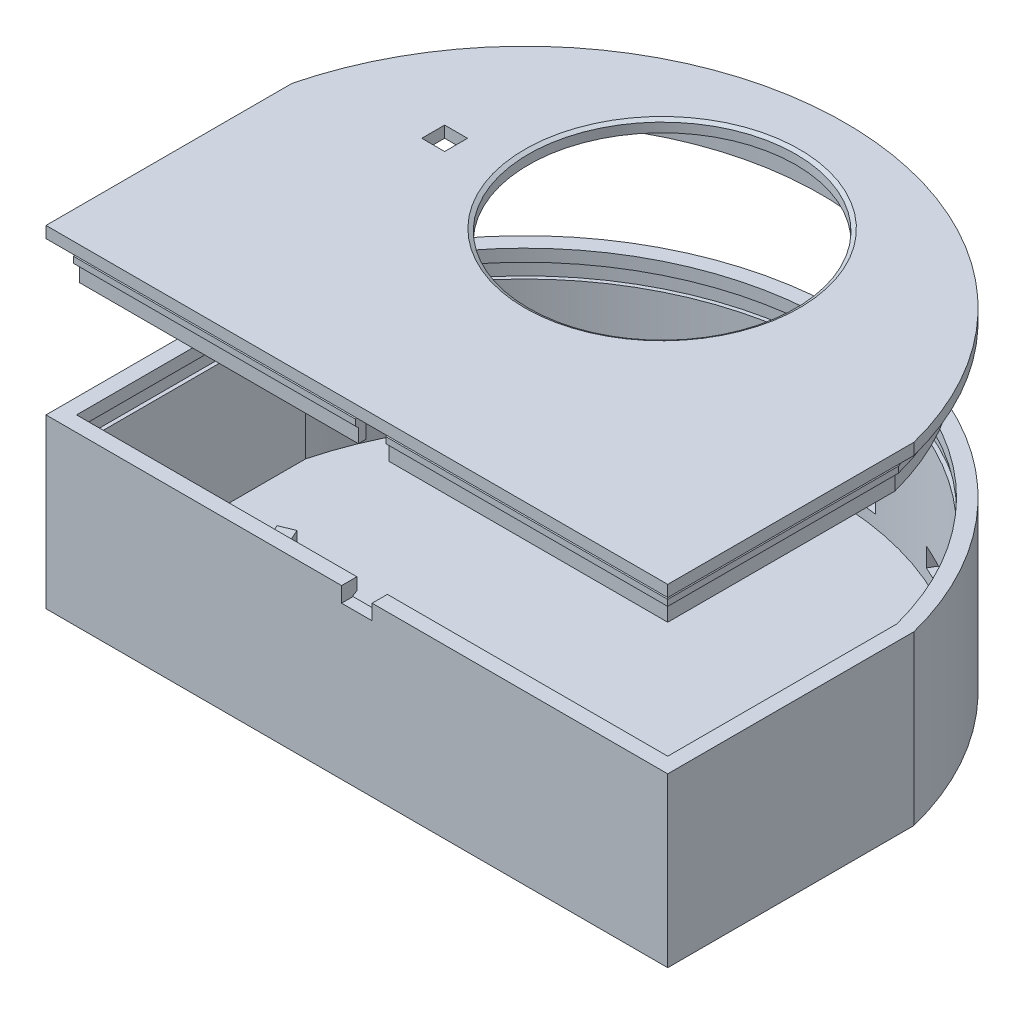
SolidWorks part; units mm, degrees
ref_plane "Front Plane" through (0, 0, 0) normal (0, 0, 1) x (1, 0, 0)
ref_plane "Top Plane" through (0, 0, 0) normal (0, 1, 0) x (1, 0, 0)
ref_plane "Right Plane" through (0, 0, 0) normal (1, 0, 0) x (0, 0, -1)
sketch "Sketch1" plane through (0, 0, 0) normal (0, 1, 0) x (1, 0, 0)
  line L0 (0, 0) -> (0, 30)
  line L1 (0, 0) -> (-38.7298, 0)
  line L2 (0, 0) -> (38.7298, 0)
  line L3 (38.7298, 0) -> (38.7298, -30)
  line L4 (38.7298, -30) -> (-38.7298, -30)
  line L5 (-38.7298, -30) -> (-38.7298, 0)
  circle A0 centre (0, 0) radius 30
  circle A1 centre (0, -10) radius 40
  dimension "D1" = 80
  dimension "D2" = 60
  dimension "D3" = 30
  dimension "D4" = 30
extrude "Base" add sketch "Sketch1" along normal blind 20 contours L5 A1 L4 A0 L1 | A1 L5 L4 | A0 A1 L1 | L0 A0 L1 | L2 A0 L0 | L2 A1 A0 | L4 A1 L3 L2 A0 | A1 L4 L3 | A0 L2 L1 region at (-12.7324, 0, -12.7324) region at (0, 0, 12.7324) region at (12.7324, 0, -12.7324) region at (29.2236, 0, -11.4068) region at (-29.2236, 0, -11.4068) region at (-29.3512, 0, 18.1812) region at (29.3512, 0, 18.1812) region at (37.4479, 0, 26.9057) region at (-37.4479, 0, 26.9057)
shell "Shell" thickness 2 removed face at (0, 20, 7.5) outward yes
sketch "Sketch2" plane through (0, 0, 0) normal (0, 1, 0) x (1, 0, 0)
  line L0 (-15.9094, 26.7) -> (-18.4094, 31.0301)
  line L1 (-18.4094, 31.0301) -> (-21.8735, 29.0301)
  line L2 (-21.8735, 29.0301) -> (-19.5026, 24.9235)
  line L3 (-38.7298, 0) -> (-38.7298, -30)
  line L4 (0, -32) -> (-2, -32)
  line L5 (-2, -32) -> (-2, -30)
  line L6 (38.7298, -30) -> (-38.7298, -30) construction
  line L7 (-40.7298, -32) -> (40.7298, -32)
  line L8 (40.7298, -32) -> (40.7298, 0.2509)
  line L9 (-40.7298, 0.2509) -> (-40.7298, -32)
  line L10 (-40.7298, -32) -> (40.7298, -32)
  line L11 (40.7298, -32) -> (40.7298, 0.2509)
  line L12 (-40.7298, 0.2509) -> (-40.7298, -32)
  line L13 (-2, -30) -> (2, -30)
  line L14 (2, -30) -> (2, -32)
  line L15 (0, 30) -> (0, 26.7)
  line L16 (0, 26.7) -> (-15.9094, 26.7)
  line L17 (-6.5, 26.7) -> (-6.5, 33.7)
  line L18 (0, 26.7) -> (15.9094, 26.7)
  line L19 (6.5, 26.7) -> (6.5, 33.7)
  line L20 (-38.7298, -30) -> (38.7298, -30)
  line L21 (38.7298, -30) -> (38.7298, 0)
  line L22 (15.9094, 26.7) -> (18.4094, 31.0301)
  line L23 (18.4094, 31.0301) -> (21.8735, 29.0301)
  line L24 (21.8735, 29.0301) -> (19.5026, 24.9235)
  line L26 (-6.5, 33.7) -> (6.5, 33.7)
  line L27 (-27.4102, 17.4622) -> (27.4102, -17.4622)
  line L28 (-30.0261, 12.4372) -> (30.0261, -12.4372)
  line L29 (-27.4102, 17.4622) -> (27.4102, 17.4622)
  line L30 (27.4102, 17.4622) -> (-27.4102, -17.4622)
  line L31 (30.0261, 12.4372) -> (30.0261, -12.4372)
  line L32 (30.0261, 12.4372) -> (-30.0261, -12.4372)
  arc A0 (38.7298, 0) -> (-38.7298, 0) centre (0, -10) ccw
  arc A1 (38.7298, 0) -> (-38.7298, 0) centre (0, -10) ccw construction
  circle A2 centre (0, 0) radius 30.5 construction
  arc A3 (40.7298, 0.2509) -> (-40.7298, 0.2509) centre (0, -10) ccw
  arc A4 (40.7298, 0.2509) -> (-40.7298, 0.2509) centre (0, -10) ccw
  circle A5 centre (0, 0) radius 32.5 construction
  arc A6 (40.6663, 0.5) -> (-40.6663, 0.5) centre (0, -10) ccw
  arc A7 (-27.4102, 17.4622) -> (-27.4102, -17.4622) centre (0, 0) ccw
  arc A8 (27.4102, 17.4622) -> (27.4102, -17.4622) centre (0, 0) cw
  arc A9 (-25.7234, 16.3876) -> (-25.7234, -16.3876) centre (0, 0) ccw
  arc A10 (25.7234, 16.3876) -> (25.7234, -16.3876) centre (0, 0) cw
  arc M15 (38.7298, 0) -> (-38.7298, 0) centre (0, -10) ccw
  line M17 (-38.7298, -30) -> (38.7298, -30)
  dimension "D15" = 61
  dimension "D2" = 4
  dimension "D3" = 2
  dimension "D4" = 6.5
  dimension "D5" = 6.5
  dimension "D6" = 3.3
  dimension "D7" = 2
  dimension "D8" = 4
  dimension "D9" = 5
  dimension "D10" = 5
  dimension "D11" = 4
  dimension "D12" = 7
  dimension "D13" = 120
  dimension "D14" = 120
  dimension "D17" = 115
  dimension "D18" = 45
  dimension "D1" = 0
  dimension "D16" = 2
extrude "Buttons" cut sketch "Sketch2" along normal blind 2.5 from offset 1.6 contours L0 A4 L2 M15 | L24 A4 L22 M15 region at (-18.2221, 0, -26.7098) region at (18.2221, 0, -26.7098)
extrude "Charging_Port" cut sketch "Sketch2<3>" along normal blind 8 from offset 1.6 contours L19 A4 L17 M15 region at (0, 0, -30.8269)
sketch "Sketch2<3>" plane through (0, 0, 0) normal (0, 1, 0) x (1, 0, 0) same geometry as "Sketch2"
extrude "Pry_Hole" cut sketch "Sketch2<4>" along normal through all from offset 18 contours L14 L5 L4 L10 M17 region at (0, 0, 31)
sketch "Sketch2<4>" plane through (0, 0, 0) normal (0, 1, 0) x (1, 0, 0) same geometry as "Sketch2"
extrude "PCB_Holder" add sketch "Sketch2<6>" along normal blind 3 contours A9 L27 A7 L28 | A9 L32 A7 L30 | L28 A10 L27 A8 | L30 A10 L32 A8 region at (-27.9148, 0, -14.5315) region at (27.9148, 0, -14.5315) region at (-27.9148, 0, 14.5315) region at (27.9148, 0, 14.5315)
sketch "Sketch2<6>" plane through (0, 0, 0) normal (0, 1, 0) x (1, 0, 0) same geometry as "Sketch2"
sketch "Sketch4" plane through (0, 20, 0) normal (0, 1, 0) x (1, 0, 0)
  line L3 (39.2298, -30.5) -> (39.2298, 0.0633)
  line L4 (-39.2298, 0.0633) -> (-39.2298, -30.5)
  line L5 (-39.2298, -30.5) -> (39.2298, -30.5)
  line L6 (38.7298, -30) -> (38.7298, 0)
  line L7 (-38.7298, -30) -> (38.7298, -30)
  line L8 (-38.7298, 0) -> (-38.7298, -30)
  line L9 (38.7298, -30) -> (38.7298, 0)
  line L10 (-38.7298, -30) -> (38.7298, -30)
  line L11 (-38.7298, 0) -> (-38.7298, -30)
  arc A1 (39.2298, 0.0633) -> (-39.2298, 0.0633) centre (0, -10) ccw
  arc A2 (38.7298, 0) -> (-38.7298, 0) centre (0, -10) ccw
  arc A3 (38.7298, 0) -> (-38.7298, 0) centre (0, -10) ccw
  dimension "D1" = 0
  dimension "D2" = 0.5
extrude "Snap_Fit_Female" cut sketch "Sketch4" against normal blind 1.5 from offset 2 offset against normal yes
chamfer "Snap_Fit_Female_Chamfer" distance 0.4 angle 60 5 edges at (-20.3649, 18, 30) (20.3649, 18, 30) (38.7298, 18, 15) (-38.7298, 18, 15) (0, 18, -30) first distance on face at (-20.3649, 19, 30) first distance on face at (20.3649, 19, 30) first distance on face at (38.7298, 19, 15) first distance on face at (-38.7298, 19, 15) first distance on face at (0, 19, -15)
sketch "Sketch5" plane through (0, 20, 0) normal (0, 1, 0) x (1, 0, 0)
  line L0 (0, 0) -> (-24.5, 0)
  line L1 (-24.5, 0) -> (-26, 0)
  line L2 (-26, 0) -> (-26, 2.5)
  line L3 (-24.5, 0) -> (-24.5, 4)
  line L5 (38.5298, -29.8) -> (38.5298, -0.0254)
  line L6 (-38.5298, -0.0254) -> (-38.5298, -29.8)
  line L7 (-38.5298, -29.8) -> (-2, -29.8)
  line L8 (-2, -29.8) -> (2, -29.8)
  line L9 (2, -29.8) -> (38.5298, -29.8)
  line L10 (40.7298, -32) -> (40.7298, 0.2509)
  line L11 (2, -32) -> (40.7298, -32)
  line L12 (-2, -32) -> (2, -32)
  line L13 (-40.7298, -32) -> (-2, -32)
  line L14 (-40.7298, 0.2509) -> (-40.7298, -32)
  line L15 (40.7298, -32) -> (40.7298, 0.2509)
  line L16 (2, -32) -> (40.7298, -32)
  line L17 (-2, -32) -> (2, -32)
  line L18 (-40.7298, -32) -> (-2, -32)
  line L19 (-40.7298, 0.2509) -> (-40.7298, -32)
  line L20 (37.5298, -28.8) -> (37.5298, -0.1536)
  line L21 (-37.5298, -0.1536) -> (-37.5298, -28.8)
  line L22 (-37.5298, -28.8) -> (-2, -28.8)
  line L23 (-2, -28.8) -> (2, -28.8)
  line L24 (2, -28.8) -> (37.5298, -28.8)
  line L25 (-2, -28.8) -> (-2, -32)
  line L26 (2, -28.8) -> (2, -32)
  line L27 (38.9298, -30.2) -> (38.9298, 0.0254)
  line L28 (-38.9298, 0.0254) -> (-38.9298, -30.2)
  line L29 (-38.9298, -30.2) -> (-2, -30.2)
  line L30 (-2, -30.2) -> (2, -30.2)
  line L31 (2, -30.2) -> (38.9298, -30.2)
  line L32 (0, 32) -> (0, 25.5)
  line L33 (-26, 2.5) -> (-23, 2.5)
  line L34 (-26, 2.5) -> (-26, 5.5)
  line L35 (-26, 5.5) -> (-23, 5.5)
  line L36 (-23, 2.5) -> (-23, 5.5)
  arc A1 (38.5298, -0.0254) -> (-38.5298, -0.0254) centre (0, -10) ccw
  arc A2 (40.7298, 0.2509) -> (-40.7298, 0.2509) centre (0, -10) ccw
  arc A3 (40.7298, 0.2509) -> (-40.7298, 0.2509) centre (0, -10) ccw
  arc A4 (37.5298, -0.1536) -> (-37.5298, -0.1536) centre (0, -10) ccw
  arc A5 (38.9298, 0.0254) -> (-38.9298, 0.0254) centre (0, -10) ccw
  circle A6 centre (0, 8) radius 17.5
  line M19 (38.7298, -30) -> (2, -30)
  line M20 (2, -30) -> (2, -32)
  line M21 (2, -32) -> (40.7298, -32)
  line M22 (40.7298, -32) -> (40.7298, 0.2509)
  arc M23 (40.7298, 0.2509) -> (-40.7298, 0.2509) centre (0, -10) ccw
  line M24 (-40.7298, 0.2509) -> (-40.7298, -32)
  line M25 (-40.7298, -32) -> (-2, -32)
  line M26 (-2, -32) -> (-2, -30)
  line M27 (-2, -30) -> (-38.7298, -30)
  line M28 (-38.7298, -30) -> (-38.7298, 0)
  arc M29 (-38.7298, 0) -> (38.7298, 0) centre (0, -10) cw
  line M30 (38.7298, 0) -> (38.7298, -30)
  dimension "D6" = 35
  dimension "D5" = 6.5
  dimension "D7" = 24.5
  dimension "D8" = 1.5
  dimension "D9" = 2.5
  dimension "D10" = 4
  dimension "D11" = 3
  dimension "D12" = 3
  dimension "D1" = 0
  dimension "D2" = 2.2
  dimension "D3" = 1
  dimension "D4" = 0.4
extrude "Lid" add sketch "Sketch5" along normal blind 1.5 from offset 20 separate body contours A5 L32 L29 L28 M23 M24 M25 M26 | A1 L32 L25 L7 L6 M29 M28 M27 | L32 A5 L28 L29 L25 M27 M28 M29 | A4 L32 A1 L6 L7 L25 L22 L21 | A6 A4 L21 L22 L23 L24 L20 L1 L2 L34 L35 L36 L33 L3 | L33 L2 L1 L3 | L30 L17 L26 M26 | L26 L23 L25 L8 | L25 L30 L26 L8 M20 | A4 L20 L24 L26 L9 L5 A1 L32 | A1 L5 L9 L26 L32 M19 M30 M29 | L27 A5 L32 L31 M29 M30 M19 M20 | A5 L27 L31 L26 L32 M21 M22 M23 region at (-25.25, 20, -1.25) region at (23.1223, 20, -19.9712) region at (-24.1337, 20, -21.2823) region at (0.7097, 20, -29.3) region at (-24.4061, 20, -21.5289) region at (0.7141, 20, -29.9) region at (-24.5389, 20, -21.6796) region at (0.7186, 20, -30.1) region at (-25.0922, 20, -22.3727) region at (0.7586, 20, -31.1) region at (0, 20, 29.3) region at (0, 20, 30) region at (0, 20, 31.1)
chamfer "Display_Chamfer" distance 0.5 angle 30 1 edges at (0, 41.5, 9.5) first distance on face at (-24.5, 41.5, -4)
extrude "Lid_Inner_Wall" add sketch "Sketch5<5>" against normal blind 5 from offset 20 contours A4 L32 A1 L6 L7 L25 L22 L21 | A4 L20 L24 L26 L9 L5 A1 L32 region at (-24.1337, 20, -21.2823) region at (0.7097, 20, -29.3)
sketch "Sketch5<5>" plane through (0, 20, 0) normal (0, 1, 0) x (1, 0, 0) same geometry as "Sketch5"
extrude "Snap_Fit_Male" add sketch "Sketch5<6>" against normal blind 1.6 from offset 18.4 contours A1 L32 L25 L7 L6 M29 M28 M27 | L32 A5 L28 L29 L25 M27 M28 M29 | A1 L5 L9 L26 L32 M19 M30 M29 | L27 A5 L32 L31 M29 M30 M19 M20 region at (-24.4061, 20, -21.5289) region at (0.7141, 20, -29.9) region at (-24.5389, 20, -21.6796) region at (0.7186, 20, -30.1)
sketch "Sketch5<6>" plane through (0, 20, 0) normal (0, 1, 0) x (1, 0, 0) same geometry as "Sketch5"
chamfer "Snap_Fit_Male_Chamfer" distance 0.4 angle 45 10 edges at (-20.4649, 36.8, 30.2) (-20.4649, 38.4, 30.2) (20.4649, 36.8, 30.2) (38.9298, 36.8, 15.0873) (0, 36.8, -30.2) (-38.9298, 36.8, 15.0873) (20.4649, 38.4, 30.2) (38.9298, 38.4, 15.0873) (0, 38.4, -30.2) (-38.9298, 38.4, 15.0873)
